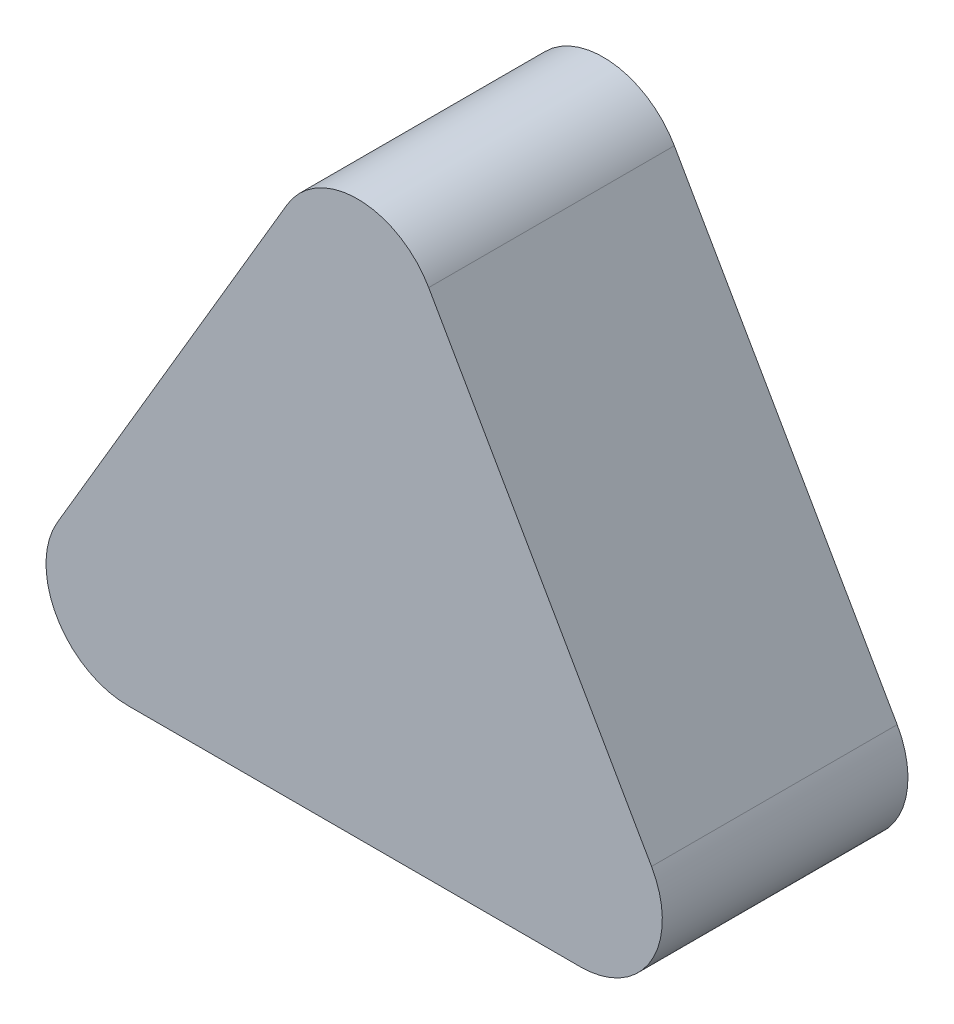
SolidWorks part; units mm, degrees
ref_plane "前视基准面" through (0, 0, 0) normal (0, 0, 1) x (1, 0, 0)
ref_plane "上视基准面" through (0, 0, 0) normal (0, 1, 0) x (1, 0, 0)
ref_plane "右视基准面" through (0, 0, 0) normal (1, 0, 0) x (0, 0, -1)
sketch "草图1" plane through (0, 0, 0) normal (0, 0, 1) x (1, 0, 0)
  line L0 (-90, 0) -> (0, 0)
  line L3 (-44.3161, 77.5434) -> (-90, 0)
  line L7 (0, 0) -> (-44.3161, 77.5434)
extrude "凸台-拉伸1" add sketch "草图1" along normal blind 30
fillet "圆角1" radius 10 3 edges at (0, 0, 15) (-44.3161, 77.5434, 15) (-90, 0, 15)
scale "缩放比例1" scale about origin uniform scaling yes scale factor 2
ref_point "点2"
ref_point "点4"
ref_point "点6"
sketch "草图3" plane through (-133.6217, 78.722, 0) normal (-0.8616, 0.5076, 0) x (0, 0, 1)
  line L0 (30, -1.103) -> (30, -21.103)
sketch "草图4" plane through (0, 0, 0) normal (0, -1, 0) x (-1, 0, 0)
  line L0 (89.7351, -30) -> (69.7351, -30)
sketch "草图5" plane through (0, 0, 0) normal (0.8682, 0.4962, 0) x (0, 0, -1)
  line L0 (-30, 89.3134) -> (-30, 109.3134)
ref_axis "基准轴2" through (-89.7351, 0, 30) along (1, 0, 0)
ref_axis "基准轴3" through (-44.3161, 77.5434, 30) along (-0.4962, 0.8682, 0)
ref_axis "基准轴4" through (-134.1816, 77.7717, 30) along (-0.5076, -0.8616, 0)
ref_axis "基准轴5" through (-89.7351, 0, 30) along (0, -1, 0)
ref_axis "基准轴6" through (-44.3161, 77.5434, 30) along (0.8682, 0.4962, 0)
ref_axis "基准轴7" through (-134.1816, 77.7717, 30) along (-0.8616, 0.5076, 0)
